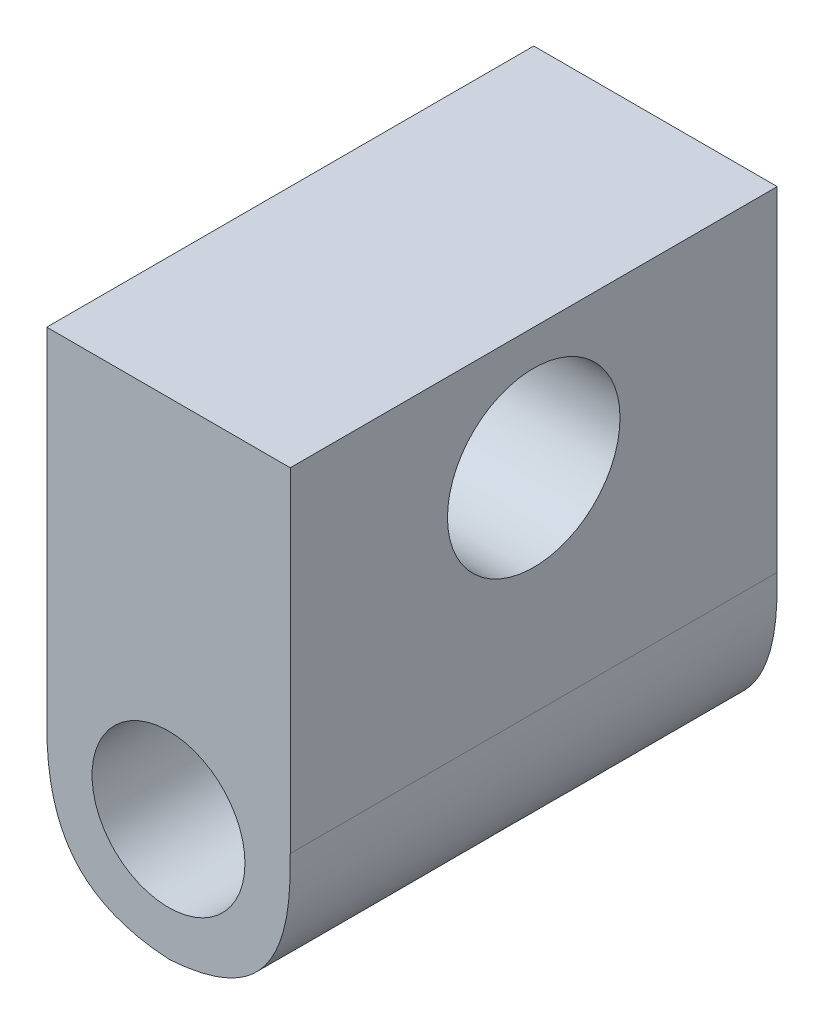
SolidWorks part; units mm, degrees
ref_plane "Front Plane" through (0, 0, 0) normal (0, 0, 1) x (1, 0, 0)
ref_plane "Top Plane" through (0, 0, 0) normal (0, 1, 0) x (1, 0, 0)
ref_plane "Right Plane" through (0, 0, 0) normal (1, 0, 0) x (0, 0, -1)
sketch "Sketch1" plane through (0, 0, 0) normal (0, 0, 1) x (1, 0, 0)
  line L1 (-6.35, 6.35) -> (6.35, 6.35)
  line L2 (-6.35, 6.35) -> (-6.35, -6.35)
  line L3 (-6.35, -6.35) -> (6.35, -6.35)
  line L4 (6.35, 6.35) -> (6.35, -6.35)
  line L5 (-6.35, 6.35) -> (6.35, -6.35) construction
  line L6 (-6.35, -6.35) -> (6.35, 6.35) construction
  line L7 (-6.35, 6.35) -> (6.35, 6.35)
  line L8 (-6.35, 6.35) -> (-6.35, 19.05)
  line L9 (-6.35, 19.05) -> (6.35, 19.05)
  line L10 (6.35, 6.35) -> (6.35, 19.05)
  circle A0 centre (0, 0) radius 3.9878
  point P0 (0, 0)
  dimension "D2" = 7.9756
  dimension "D1" = 12.7
  dimension "D3" = 12.7
extrude "Boss-Extrude1" add sketch "Sketch1" against normal blind 25.4 contours L1 L10 L9 L8 | L4 L1 L2 L3 A0 region at (0, 12.7, 0) region at (0, 6.1704, 0)
sketch "Sketch2" plane through (-6.35, 0, 0) normal (-1, 0, 0) x (0, 0, 1)
  line L0 (0, -6.35) -> (0, 19.05) construction
  line L1 (-25.4, 19.05) -> (0, 19.05)
  line L2 (-25.4, 19.05) -> (-25.4, 6.35)
  line L3 (-25.4, 6.35) -> (0, 6.35)
  line L4 (0, 19.05) -> (0, 6.35)
  line L5 (-25.4, 19.05) -> (0, 6.35) construction
  line L6 (0, 19.05) -> (-25.4, 6.35) construction
  circle A0 centre (-12.7, 12.7) radius 4.4996
  dimension "D2" = 8.9992
  dimension "D1" = 12.7
extrude "Cut-Extrude1" cut sketch "Sketch2" against normal up to surface (12.7 mm away) contours A0 region at (-6.35, 12.7, -12.7) up to face at (6.35, 6.35, -12.7)
fillet "Fillet1" radius 7.9756 2 edges at (-6.35, -6.35, -12.7) (6.35, -6.35, -12.7) curvature continuous yes
